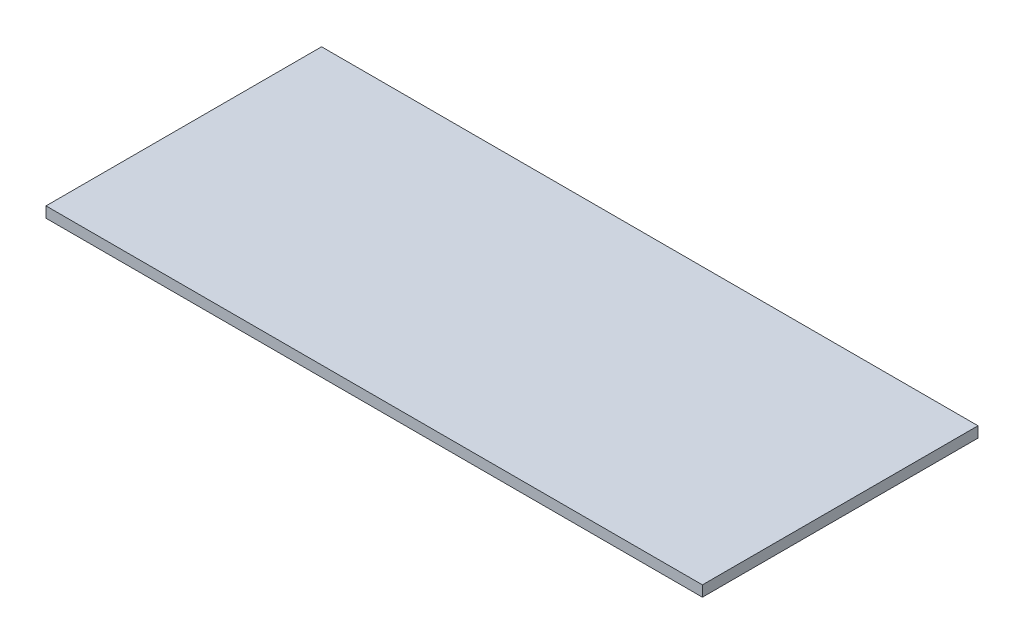
SolidWorks part; units mm, degrees
ref_plane "Front Plane" through (0, 0, 0) normal (0, 0, 1) x (1, 0, 0)
ref_plane "Top Plane" through (0, 0, 0) normal (0, 1, 0) x (1, 0, 0)
ref_plane "Right Plane" through (0, 0, 0) normal (1, 0, 0) x (0, 0, -1)
sketch "Sketch1" plane through (0, 0, 0) normal (0, 1, 0) x (1, 0, 0)
  line L1 (0, 0) -> (155.4028, 0)
  line L2 (0, 0) -> (0, 65.2415)
  line L3 (0, 65.2415) -> (155.4028, 65.2415)
  line L4 (155.4028, 0) -> (155.4028, 65.2415)
extrude "Boss-Extrude1" add sketch "Sketch1" along normal blind 2.54
